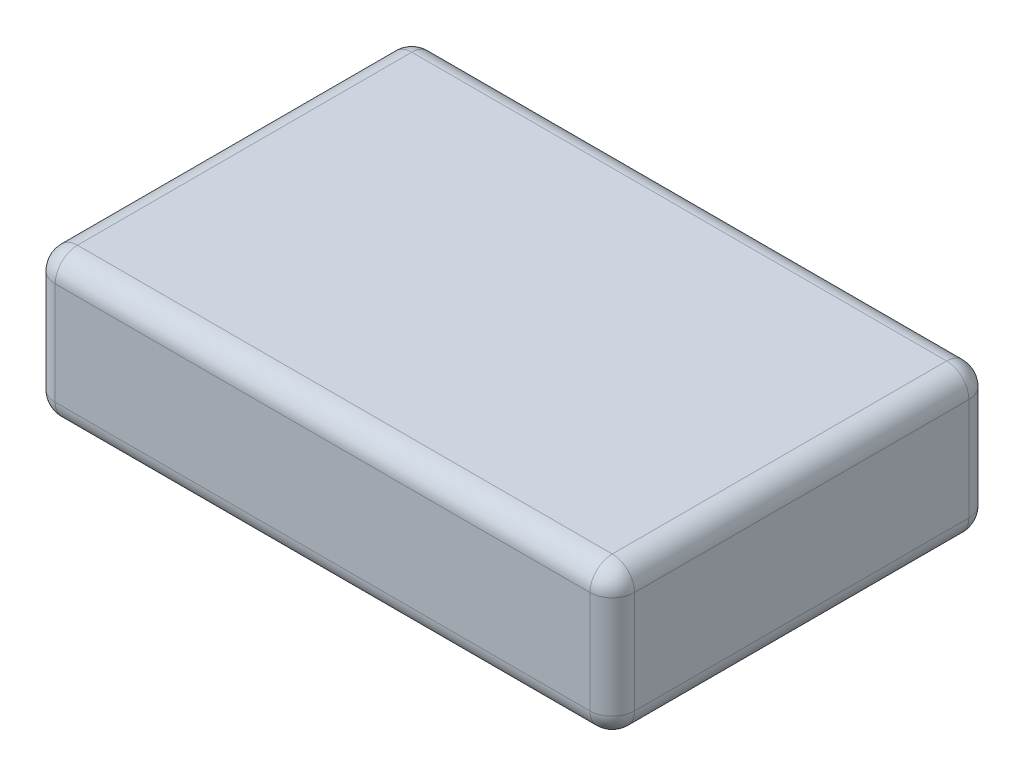
SolidWorks part; units mm, degrees
ref_plane "Front Plane" through (0, 0, 0) normal (0, 0, 1) x (1, 0, 0)
ref_plane "Top Plane" through (0, 0, 0) normal (0, 1, 0) x (1, 0, 0)
ref_plane "Right Plane" through (0, 0, 0) normal (1, 0, 0) x (0, 0, -1)
sketch "Sketch1" plane through (0, 0, 0) normal (0, 1, 0) x (1, 0, 0)
  line L1 (-13, -8.5) -> (13, -8.5)
  line L2 (-13, -8.5) -> (-13, 8.5)
  line L3 (-13, 8.5) -> (13, 8.5)
  line L4 (13, -8.5) -> (13, 8.5)
  line L5 (-13, -8.5) -> (13, 8.5) construction
  line L6 (-13, 8.5) -> (13, -8.5) construction
  point P0 (0, 0)
  dimension "D1" = 26
  dimension "D2" = 17
extrude "Boss-Extrude1" add sketch "Sketch1" along normal blind 6.6
fillet "Fillet1" radius 1 12 edges at (-13, 3.3, -8.5) (-13, 3.3, 8.5) (13, 3.3, 8.5) (13, 3.3, -8.5) (0, 0, -8.5) (-13, 0, 0) (0, 0, 8.5) (13, 0, 0) (0, 6.6, 8.5) (-13, 6.6, 0) (0, 6.6, -8.5) (13, 6.6, 0)
